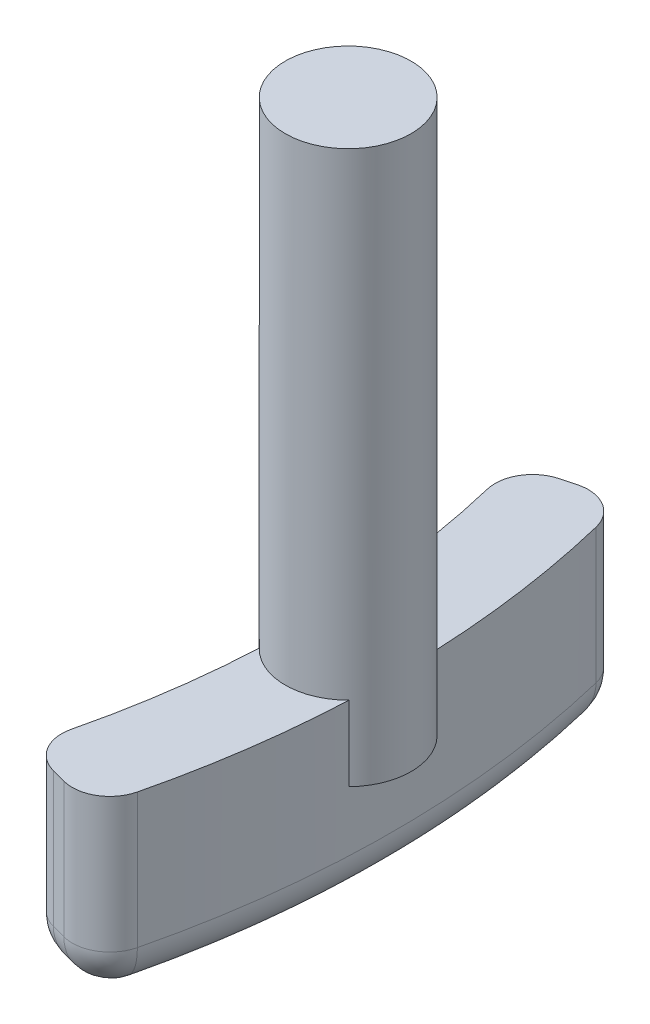
SolidWorks part; units mm, degrees
material "ABS"
ref_plane "Front Plane" through (0, 0, 0) normal (0, 0, 1) x (1, 0, 0)
ref_plane "Top Plane" through (0, 0, 0) normal (0, 1, 0) x (1, 0, 0)
ref_plane "Right Plane" through (0, 0, 0) normal (1, 0, 0) x (0, 0, -1)
sketch "Эскиз1" plane through (0, 0, 0) normal (0, 1, 0) x (1, 0, 0)
  line L8 (-0.9714, -8.4393) -> (-0.4883, -8.5687)
  line L9 (-0.9714, 8.4393) -> (-0.4883, 8.5687)
  arc A24 (-0.4883, -8.5687) -> (1.0501, -7.6558) centre (-0.1648, -7.3613) ccw
  arc A25 (1.0501, 7.6558) -> (1.0501, -7.6558) centre (-30.5354, 0) cw
  arc A26 (1.0501, 7.6558) -> (-0.4883, 8.5687) centre (-0.1648, 7.3613) ccw
  arc A27 (-0.9714, 8.4393) -> (-1.8628, 6.9379) centre (-0.6479, 7.2319) ccw
  arc A28 (-1.8628, 6.9379) -> (-1.8628, -6.9379) centre (-30.5354, 0) cw
  arc A29 (-0.9714, -8.4393) -> (-1.8628, -6.9379) centre (-0.6479, -7.2319) cw
  point P13 (0.3409, 8.2822)
  point P14 (0.3409, -8.2822)
extrude "Бобышка-Вытянуть1" add sketch "Эскиз1" along normal blind 5
ref_plane "Плоскость1" through (0, 2.5, 0) normal (0, 1, 0) x (1, 0, 0)
sketch "Эскиз2" plane through (0, 2.5, 0) normal (0, 1, 0) x (1, 0, 0)
  circle A2 centre (0.4313, 0) radius 2.1
  dimension "D1" = 4.2
extrude "Бобышка-Вытянуть2" add sketch "Эскиз2" along normal blind 18.44
sketch "Эскиз3" plane through (0, 0, 0) normal (0, -1, 0) x (1, 0, 0)
  line L10 (-0.4883, -8.5687) -> (-0.9714, -8.4393) construction
  line L11 (-0.9714, 8.4393) -> (-0.4883, 8.5687) construction
  line L12 (-0.4883, -8.5687) -> (-0.9714, -8.4393)
  line L13 (-0.9714, 8.4393) -> (-0.4883, 8.5687)
  arc A30 (-0.4883, -8.5687) -> (1.0501, -7.6558) centre (-0.1648, -7.3613) ccw construction
  arc A31 (-1.8628, -6.9379) -> (-0.9714, -8.4393) centre (-0.6479, -7.2319) ccw construction
  arc A32 (1.0501, -7.6558) -> (1.0501, 7.6558) centre (-30.5354, 0) ccw construction
  arc A33 (1.0501, 7.6558) -> (-0.4883, 8.5687) centre (-0.1648, 7.3613) ccw construction
  arc A34 (-0.9714, 8.4393) -> (-1.8628, 6.9379) centre (-0.6479, 7.2319) ccw construction
  arc A35 (-1.8628, -6.9379) -> (-1.8628, 6.9379) centre (-30.5354, 0) ccw construction
  arc A36 (-0.4883, -8.5687) -> (1.0501, -7.6558) centre (-0.1648, -7.3613) ccw
  arc A37 (-1.8628, -6.9379) -> (-0.9714, -8.4393) centre (-0.6479, -7.2319) ccw
  arc A38 (1.0501, -7.6558) -> (1.0501, 7.6558) centre (-30.5354, 0) ccw
  arc A39 (1.0501, 7.6558) -> (-0.4883, 8.5687) centre (-0.1648, 7.3613) ccw
  arc A40 (-0.9714, 8.4393) -> (-1.8628, 6.9379) centre (-0.6479, 7.2319) ccw
  arc A41 (-1.8628, -6.9379) -> (-1.8628, 6.9379) centre (-30.5354, 0) ccw
  point P27 (0, 0)
extrude "Бобышка-Вытянуть3" add sketch "Эскиз3" along normal blind 1
fillet "Скругление2" radius 1.5 8 edges at (-1.7227, -1, 7.87) (-0.7298, -1, 8.504) (0.4732, -1, 8.4363) (1.9646, -1, 0) (0.4732, -1, -8.4363) (-0.7298, -1, -8.504) (-1.7227, -1, -7.87) (-1.0354, -1, 0)
